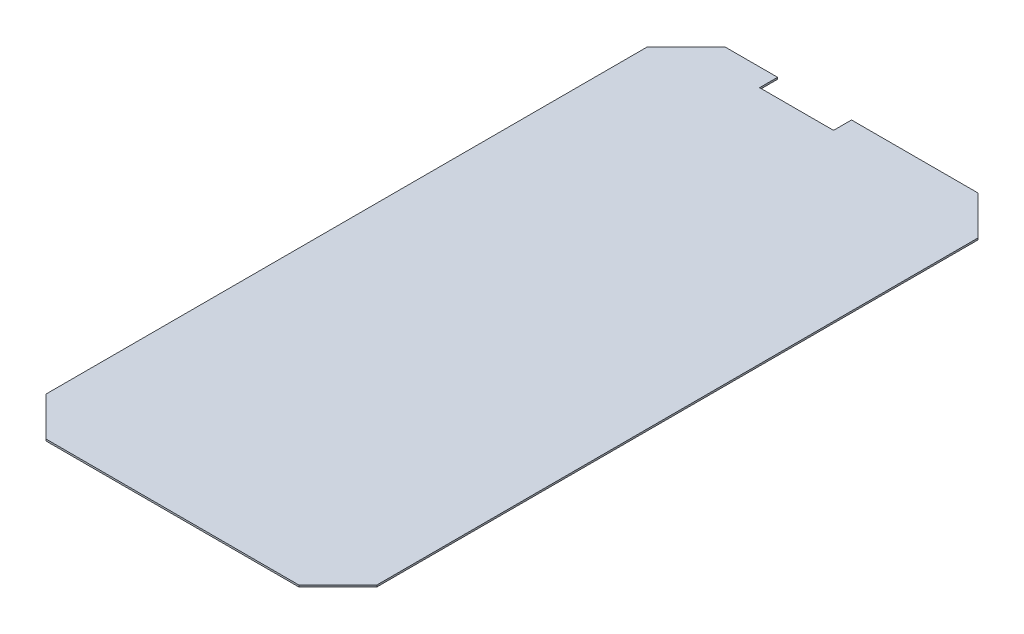
SolidWorks part; units mm, degrees
ref_plane "Front Plane" through (0, 0, 0) normal (0, 0, 1) x (1, 0, 0)
ref_plane "Top Plane" through (0, 0, 0) normal (0, 1, 0) x (1, 0, 0)
ref_plane "Right Plane" through (0, 0, 0) normal (1, 0, 0) x (0, 0, -1)
ref_axis "X-Axis" through (-88.99, 0, 0) along (1, 0, 0)
ref_axis "Y-Axis" through (0, 55, 0) along (0, -1, 0)
ref_axis "Z-Axis" through (0, 0, -88.99) along (0, 0, 1)
sketch "Sketch1" plane through (0, 0, 0) normal (0, 1, 0) x (1, 0, 0)
  line L1 (-17, -34.9) -> (17, -34.9)
  line L2 (-17, -34.9) -> (-17, 34.9)
  line L3 (-17, 34.9) -> (17, 34.9)
  line L4 (17, -34.9) -> (17, 34.9)
  line L5 (-17, -34.9) -> (17, 34.9) construction
  line L6 (-17, 34.9) -> (17, -34.9) construction
  point P0 (0, 0)
  dimension "D1" = 69.8
  dimension "D2" = 34
extrude "Boss-Extrude1" add sketch "Sketch1" along normal blind 0.18
chamfer "Chamfer1" distance 4 angle 45 4 edges at (-17, 0.09, 34.9) (17, 0.09, -34.9) (-17, 0.09, -34.9) (17, 0.09, 34.9)
sketch "Sketch2" plane through (0, 0.18, 0) normal (0, 1, 0) x (1, 0, 0)
  line L0 (13, 34.9) -> (-13, 34.9) construction
  line L1 (-7.6, 34.9) -> (0, 34.9)
  line L2 (-7.6, 34.9) -> (-7.6, 33.05)
  line L3 (-7.6, 33.05) -> (0, 33.05)
  line L4 (0, 34.9) -> (0, 33.05)
  line L5 (-17, 30.9) -> (-17, -30.9) construction
  dimension "D1" = 9.4
  dimension "D2" = 1.85
  dimension "D3" = 7.6
extrude "Cut-Extrude1" cut sketch "Sketch2" against normal through all
